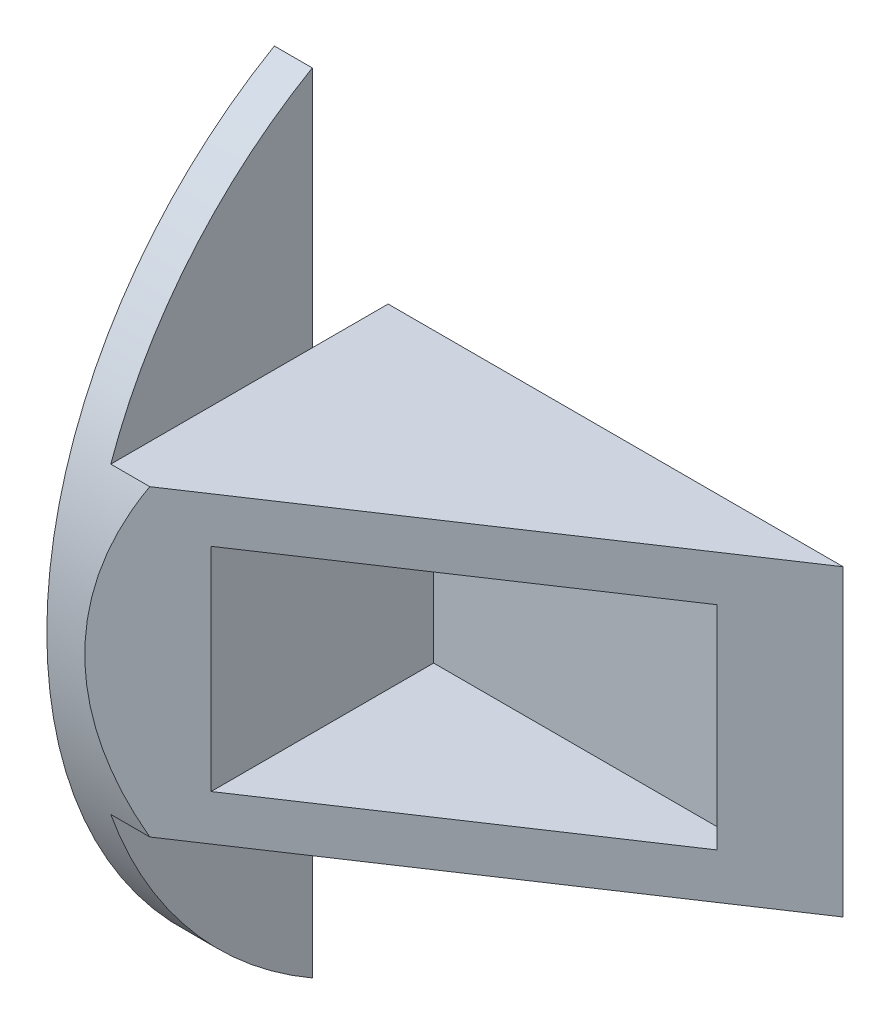
SolidWorks part; units mm, degrees
ref_plane "Front Plane" through (0, 0, 0) normal (0, 0, 1) x (1, 0, 0)
ref_plane "Top Plane" through (0, 0, 0) normal (0, 1, 0) x (1, 0, 0)
ref_plane "Right Plane" through (0, 0, 0) normal (1, 0, 0) x (0, 0, -1)
sketch "Sketch1" plane through (0, 0, 0) normal (0, 1, 0) x (1, 0, 0)
  line L0 (-15, -10) -> (15, 10)
  line L1 (15, 10) -> (-15, 10)
  line L2 (15, 10) -> (15, -10)
  line L3 (15, -10) -> (-15, -10)
  line L4 (-15, 10) -> (-15, -10)
  line L5 (15, 10) -> (-15, -10) construction
  line L6 (15, -10) -> (-15, 10) construction
  point P0 (0, 0)
  dimension "D1" = 20
  dimension "D2" = 30
extrude "Boss-Extrude1" add sketch "Sketch1" along normal mid plane 20 contours L1 L4 L0 region at (-5, 0, -3.3333)
sketch "Sketch2" plane through (0, 0, 0) normal (1, 0, 0) x (0, 0, -1)
  line L1 (-8, 7) -> (8, 7)
  line L2 (-8, 7) -> (-8, -7)
  line L3 (-8, -7) -> (8, -7)
  line L4 (8, 7) -> (8, -7)
  line L5 (-8, 7) -> (8, -7) construction
  line L6 (-8, -7) -> (8, 7) construction
  line L7 (10, 10) -> (10, -10) construction
  line L8 (-10, 10) -> (-10, -10) construction
  point P0 (0, 0)
  dimension "D1" = 14
  dimension "D2" = 2
  dimension "D3" = 2
extrude "Cut-Extrude1" cut sketch "Sketch2" against normal mid plane 20
sketch "Sketch3" plane through (-15, 0, 0) normal (-1, 0, 0) x (0, 0, 1)
  line L0 (-5, 25.9808) -> (-5, -25.9808)
  line L1 (-20, 30) -> (-20, -30)
  line L2 (-10, 10) -> (-10, -10) construction
  circle A0 centre (-20, 0) radius 30
  line M1 (-10, -10) -> (10, -10)
  line M3 (10, 10) -> (-10, 10)
  dimension "D1" = 60
  dimension "D2" = 10
  dimension "D3" = 15
extrude "Boss-Extrude2" add sketch "Sketch3" along normal blind 2.5 contours A0 L0 M3 | L0 A0 M1 | A0 L0 M3 M1 region at (-15, 15.9425, -0.0255) region at (-15, 0, 2.2264) region at (-15, -15.9425, -0.0255)
extrude "Cut-Extrude-Thin1" cut sketch "Sketch3<4>" against normal blind 32.5 flip side to cut thin contours A0 thin type one direction wall 10
sketch "Sketch3<4>" plane through (-15, 0, 0) normal (-1, 0, 0) x (0, 0, 1) same geometry as "Sketch3"
